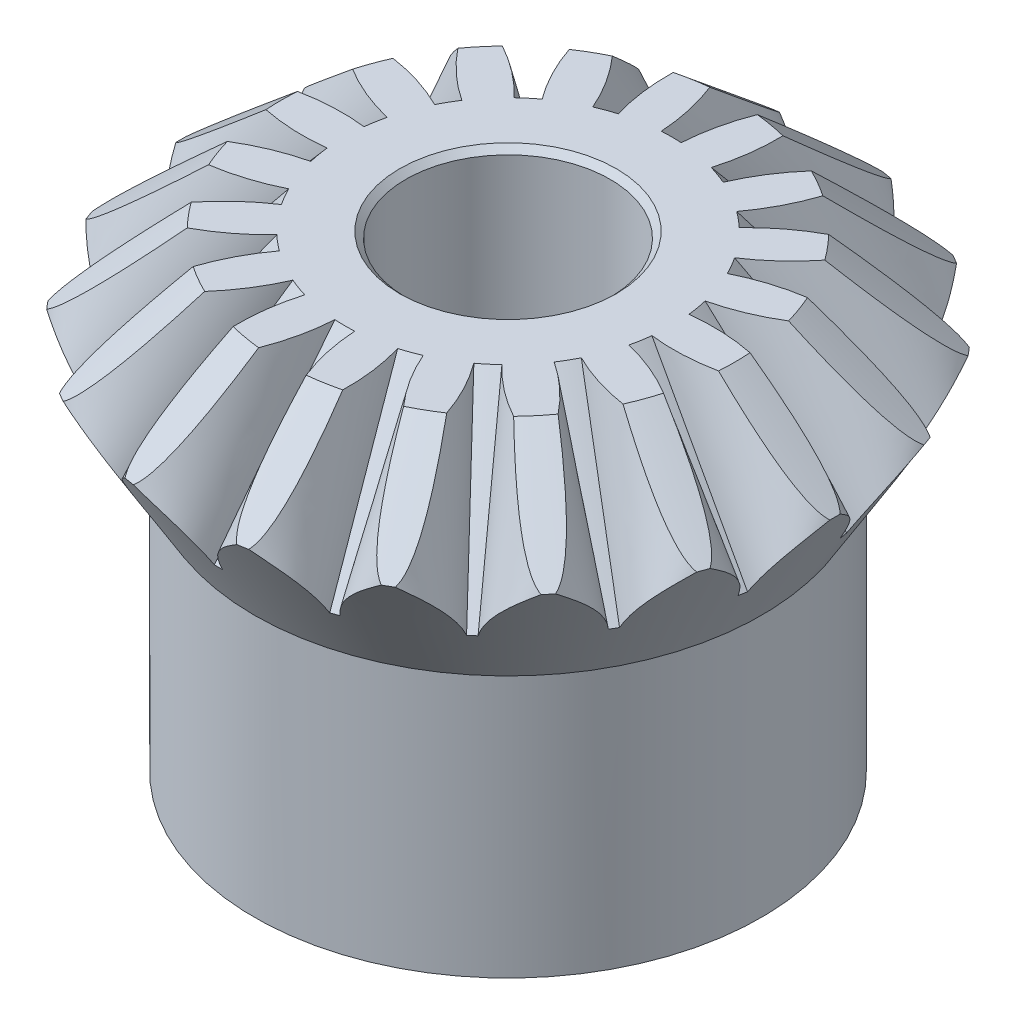
SolidWorks part; units mm, degrees
ref_plane "Front Plane" through (0, 0, 0) normal (0, 0, 1) x (1, 0, 0)
ref_plane "Top Plane" through (0, 0, 0) normal (0, 1, 0) x (1, 0, 0)
ref_plane "Right Plane" through (0, 0, 0) normal (1, 0, 0) x (0, 0, -1)
sketch "Sketch1" plane through (0, 0, 0) normal (1, 0, 0) x (0, 0, -1)
  line L0 (0, 3.6322) -> (0, -3.6322) construction
  line L1 (-3.937, -3.6322) -> (3.937, -3.6322) construction
  line L2 (3.937, -3.6322) -> (3.937, 0.4318) construction
  line L3 (-3.5234, 3.6322) -> (3.5234, 3.6322) construction
  line L4 (-5.08, 2.3261) -> (5.08, 2.3261) construction
  line L5 (5.08, 2.3261) -> (3.5234, 3.6322) construction
  line L7 (-3.5234, 3.6322) -> (-5.08, 2.3261) construction
  line L8 (0, 6.6802) -> (7.2644, 6.6802) construction
  point P0 (0, 6.6802)
  point P4 (0, 0)
  point P9 (0, -3.6322)
  point P12 (-1.5875, 3.6322)
  point P13 (1.5875, 3.6322)
  point P14 (0, 3.6322)
  point P15 (4.7625, 2.3261)
  point P18 (0, 2.3261)
  point P20 (-4.7625, 2.3261)
  dimension "Overall Width" = 7.2644
  dimension "Mounting Distance" = 10.3124
  dimension "Hub Diameter" = 7.874
  dimension "Hub Width" = 4.064
  dimension "Face Width" = 2.032
  dimension "For Shaft Diameter" = 3.175
  dimension "OD" = 10.16
  dimension "Gear Pitch Diameter" = 9.525
  dimension "For Shaft Angle" = 90
  dimension "D1" = 40
sketch "Sketch2" plane through (0, 0, 0) normal (0, 1, 0) x (1, 0, 0)
  circle A0 centre (0, 0) radius 5.08
  circle A1 centre (0, 0) radius 4.7625
  point P4 (0, -4.7625)
  point P7 (-1.6289, -4.4753)
  point P10 (-3.0613, -3.6483)
  point P11 (-4.1244, -2.3812)
  point P12 (-4.6901, -0.827)
  point P13 (-4.6901, 0.827)
  point P14 (-4.1244, 2.3813)
  point P15 (-3.0613, 3.6483)
  point P16 (-1.6289, 4.4753)
  point P17 (0, 4.7625)
  point P18 (1.6289, 4.4753)
  point P19 (3.0613, 3.6483)
  point P20 (4.1244, 2.3812)
  point P21 (4.6901, 0.827)
  point P22 (4.6901, -0.827)
  point P23 (4.1244, -2.3813)
  point P24 (3.0613, -3.6483)
  point P25 (1.6289, -4.4753)
  point P28 (0, 0)
  dimension "Number of Teeth" = 18
sketch "Sketch3" plane through (0, 0, 0) normal (1, 0, 0) x (0, 0, -1)
  line L0 (0, 3.6322) -> (-3.5234, 3.6322)
  line L1 (-3.5234, 3.6322) -> (-5.08, 2.3261)
  line L2 (-5.08, 2.3261) -> (-3.937, 0.4318)
  line L3 (-3.937, 0.4318) -> (-3.937, -3.6322)
  line L4 (-3.937, -3.6322) -> (0, -3.6322)
  line L5 (0, -3.6322) -> (0, 3.6322)
revolve "Revolve1" add sketch "Sketch3" angle 360 about L5
sketch "Sketch4" plane through (0, 3.6322, 0) normal (0, 1, 0) x (1, 0, 0)
  circle A0 centre (0, 0) radius 1.5875
extrude "Cut-Extrude1" cut sketch "Sketch4" against normal through all both and the other way through all
ref_plane "Plane1" through (0, 2.3261, 5.08) normal (0, -0.5166, 0.8562) x (1, 0, 0)
sketch "Sketch5" plane through (0, 3.6322, 0) normal (0, 1, 0) x (1, 0, 0)
  line L0 (0, 0) -> (-0.1546, -2.5353) construction
  line L1 (0, 0) -> (0.1546, -2.5353) construction
  line L2 (-3.3237, -5.517) -> (3.3237, -5.517)
  line L3 (0, -2.54) -> (0, 0) construction
  circle A0 centre (0, 0) radius 4.7625 construction
  circle A1 centre (0, 0) radius 4.7625 construction
  circle A2 centre (0, 0) radius 5.08 construction
  circle A3 centre (0, 0) radius 5.08 construction
  arc A5 (-0.1546, -2.5353) -> (0.1546, -2.5353) centre (0, 0) ccw
  arc A8 (0.1546, -2.5353) -> (3.3237, -5.517) centre (3.3237, -2.342) ccw
  arc A9 (-3.3237, -5.517) -> (-0.1546, -2.5353) centre (-3.3237, -2.342) ccw
  dimension "D1" = 3.175
  dimension "D2" = 6.98
  dimension "D3" = 2.54
sketch "Sketch6" plane through (0, 0, 0) normal (1, 0, 0) x (0, 0, -1)
  line L1 (-2.54, 3.6322) -> (-4.4971, 1.3601)
  line L2 (-2.5353, 3.6322) -> (-5.517, 3.6322) construction
  line L3 (-5.08, 2.3261) -> (-3.937, 0.4318) construction
  dimension "D1" = 49.26
sketch "Sketch7" plane through (0, 2.3261, 5.08) normal (0, -0.5166, 0.8562) x (1, 0, 0)
  line L0 (-1.7145, 0.0841) -> (1.7145, 0.0841) construction
  line L1 (0, -1.5062) -> (-0.0632, -1.1282) construction
  line L2 (0, -1.5062) -> (0.0632, -1.1282) construction
  line L3 (-0.0632, -1.1282) -> (0.0632, -1.1282)
  line L4 (-1.5119, 0.0981) -> (1.5119, 0.0981)
  arc A1 (-0.0632, -1.1282) -> (-1.5119, 0.0981) centre (-1.5119, -1.3707) ccw
  arc A2 (1.5119, 0.0981) -> (0.0632, -1.1282) centre (1.5119, -1.3707) ccw
  ellipse E1 centre (0, -2.6245) end of major axis (-4.5665, -2.6245) minor radius 2.9224 construction
  ellipse E2 centre (0, -1.5062) end of major axis (-3.5234, -1.5062) minor radius 1.8203 construction
  point P24 (0, 0.0981)
  dimension "D2" = 3.429
  dimension "D1" = 19
  dimension "D3" = 4.5665
loft "Cut-Loft1" cut profiles "Sketch5", "Sketch7" connector at (3.3237, 3.6322, 5.517) connector at (1.5119, 2.4101, 5.1307)
pattern_circular "CirPattern2" count 18 over 360 about axis through (0, 3.6322, 0) along (0, -1, 0) of "Cut-Loft1"
chamfer "Chamfer1" distance 0.0953 angle 45 2 edges at (0, -3.6322, 1.5875) (0, 3.6322, -1.5875)
sketch "Sketch8" plane through (0, 0, 0) normal (1, 0, 0) x (0, 0, -1)
  line L1 (3.048, 6.6802) -> (3.048, 10.2036)
  line L9 (3.048, 6.6802) -> (3.048, 3.1568) construction
  line L10 (3.048, 10.2036) -> (4.3541, 11.9969)
  line L14 (3.048, 3.1568) -> (4.3541, 1.6002) construction
  line L15 (4.3541, 11.9969) -> (6.2484, 10.6172)
  line L16 (6.2484, 10.6172) -> (10.3124, 10.6172)
  line L17 (10.3124, 10.6172) -> (10.3124, 6.6802)
  line L18 (10.3124, 6.6802) -> (10.3124, 2.7432)
  line L19 (10.3124, 2.7432) -> (6.2484, 2.7432)
  line L20 (6.2484, 2.7432) -> (5.08, 2.3261)
  line L21 (4.3541, 1.6002) -> (6.2484, 2.7432) construction
  line L22 (6.2484, 2.7432) -> (10.3124, 2.7432) construction
  line L23 (10.3124, 2.7432) -> (10.3124, 6.6802) construction
  line L24 (10.3124, 6.6802) -> (3.048, 6.6802) construction
  line L25 (0, 3.6322) -> (-3.5234, 3.6322)
  line L26 (-3.5234, 3.6322) -> (-5.08, 2.3261)
  line L27 (-5.08, 2.3261) -> (-3.937, 0.4318)
  line L28 (-3.937, 0.4318) -> (-3.937, -3.6322)
  line L29 (-3.937, -3.6322) -> (0, -3.6322)
  line L30 (0, -3.6322) -> (0, 3.6322)
  line L31 (0, 3.6322) -> (-3.5234, 3.6322)
  line L32 (-3.5234, 3.6322) -> (-5.08, 2.3261)
  line L33 (-5.08, 2.3261) -> (-3.937, 0.4318)
  line L34 (-3.937, 0.4318) -> (-3.937, -3.6322)
  line L35 (-3.937, -3.6322) -> (0, -3.6322)
  line L36 (0, -3.6322) -> (0, 3.6322)
  line L37 (0, 6.6802) -> (7.2644, 6.6802) construction
  line L38 (5.08, 2.3261) -> (3.5234, 3.6322)
  line L39 (3.5234, 3.6322) -> (3.048, 3.6322)
  line L40 (3.048, 3.6322) -> (3.048, 6.6802)
  line L41 (1.778, 6.6802) -> (11.5824, 6.6802)
  line L42 (0, 4.9022) -> (0, -4.9022)
  point P15 (0, 6.6802)
  point P19 (3.937, -3.6322)
  point P20 (-3.937, -3.6322)
  point P21 (-3.937, 0.4318)
  point P22 (-3.5234, 3.6322)
  point P23 (-5.08, 2.3261)
  point P25 (10.3124, 10.6172)
  point P26 (0, 3.6322)
  dimension "D3" = 1.27
  dimension "D4" = 1.27
  dimension "D5" = 1.27
  dimension "D2" = 2
sketch "Sketch9" plane through (0, 0, 0) normal (0, 1, 0) x (1, 0, 0)
  circle A0 centre (0, 0) radius 5.08
  circle A1 centre (0, 0) radius 4.7625
  circle A2 centre (0, 0) radius 1.5875 construction
  circle A3 centre (0, 0) radius 1.5875
  point P6 (0, -5.08)
  point P7 (0, 5.08)
  point P8 (0, -4.7625)
  point P9 (0, 4.7625)
  point P10 (0, -1.5875)
  point P12 (0, 1.5875)
  point P17 (-1.5875, 0)
  point P18 (1.5875, 0)
  point P19 (-4.7625, 0)
  point P20 (-5.08, 0)
  point P21 (4.7625, 0)
  point P22 (5.08, 0)
equation "\"D1@CirPattern2\"=\"Number of Teeth@Sketch2\""
equation "\"D1@Chamfer1\"=\"For Shaft Diameter@Sketch1\"*.03"
equation "\"D4@Sketch8\"=\"D3@Sketch8\""
equation "\"D5@Sketch8\"=\"D3@Sketch8\""
